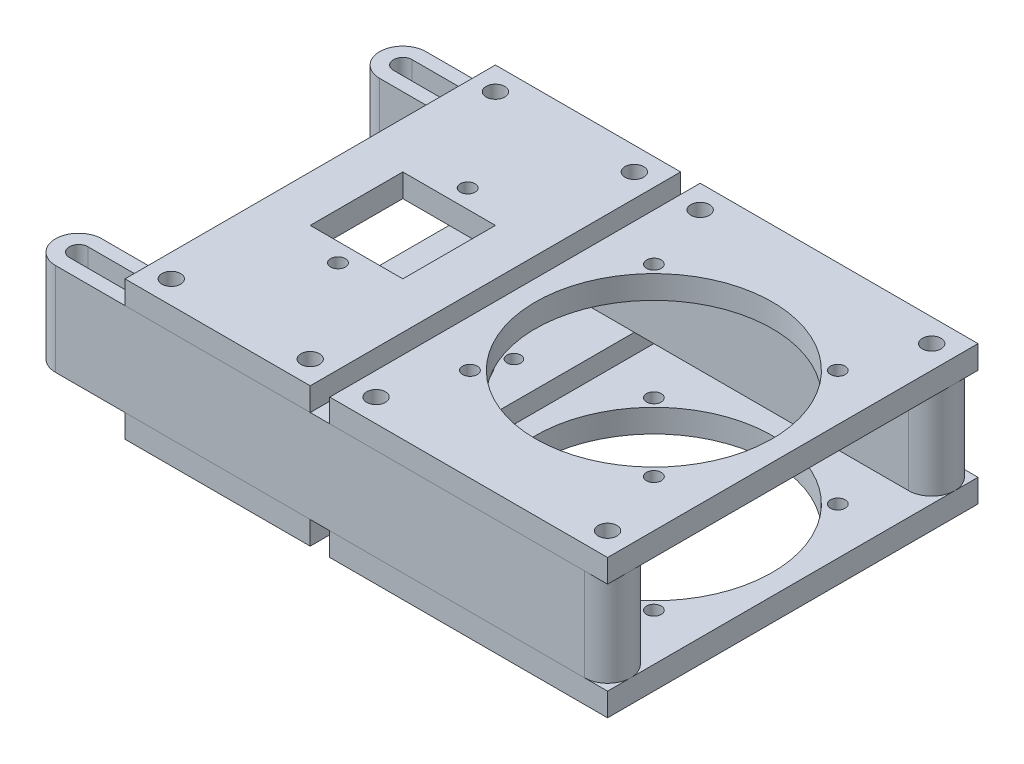
SolidWorks part; units mm, degrees
material "Alum Plate"
ref_plane "Front Plane" through (0, 0, 0) normal (0, 0, 1) x (1, 0, 0)
ref_plane "Top Plane" through (0, 0, 0) normal (0, 1, 0) x (1, 0, 0)
ref_plane "Right Plane" through (0, 0, 0) normal (1, 0, 0) x (0, 0, -1)
sketch "Sketch2" plane through (0, 0, 0) normal (0, 1, 0) x (1, 0, 0)
  line L0 (0, 0) -> (-68.8619, 0) construction
  line L1 (-38.1, -50.8) -> (-38.1, 50.8)
  line L2 (-38.1, 50.8) -> (38.1, 50.8)
  line L4 (-38.1, -50.8) -> (38.1, -50.8)
  line L5 (38.1, 50.8) -> (38.1, -50.8)
  line L7 (-94.2619, 50.8) -> (-43.4619, 50.8)
  line L8 (-81.5619, 12.7) -> (-56.1619, 12.7) construction
  line L9 (-81.5619, 12.7) -> (-81.5619, -12.7) construction
  line L10 (-81.5619, -12.7) -> (-56.1619, -12.7) construction
  line L11 (-56.1619, 12.7) -> (-56.1619, -12.7) construction
  line L12 (-81.5619, 12.7) -> (-56.1619, -12.7) construction
  line L13 (-81.5619, -12.7) -> (-56.1619, 12.7) construction
  line L14 (-38.1, -50.8) -> (38.1, 50.8) construction
  line L15 (-94.2619, 50.8) -> (-94.2619, -50.8)
  line L16 (-94.2619, -50.8) -> (-43.4619, -50.8)
  line L17 (-43.4619, 50.8) -> (-43.4619, -50.8)
  line L18 (-94.2619, 50.8) -> (-43.4619, -50.8) construction
  line L19 (-94.2619, -50.8) -> (-43.4619, 50.8) construction
  circle A0 centre (0, 0) radius 32.5
  circle A1 centre (-68.8619, 0) radius 18 construction
  point P5 (-34.431, 0)
  point P8 (-38.1, 0)
  dimension "D1" = 65
  dimension "D2" = 36
  dimension "D3" = 68.8619
  dimension "D4" = 38.1
  dimension "D5" = 50.8
  dimension "D6" = 25.4
  dimension "D7" = 25.4
  dimension "D8" = 50.8
extrude "Boss-Extrude1" add sketch "Sketch2" against normal blind 6.35 from offset 19.05
mirror "Mirror1" about plane through (0, 0, 0) normal (0, 1, 0) of bodies 101 109
sketch "Sketch3" plane through (0, 19.05, 0) normal (0, 1, 0) x (1, 0, 0)
  line L1 (-81.5619, -12.7) -> (-56.1619, -12.7)
  line L2 (-81.5619, -12.7) -> (-81.5619, 12.7)
  line L3 (-81.5619, 12.7) -> (-56.1619, 12.7)
  line L4 (-56.1619, -12.7) -> (-56.1619, 12.7)
  line L5 (-81.5619, -12.7) -> (-56.1619, 12.7) construction
  line L6 (-81.5619, 12.7) -> (-56.1619, -12.7) construction
  point P4 (-68.8619, 0)
extrude "Cut-Extrude1" cut sketch "Sketch3" against normal up to next (6.35 mm away)
sketch "Sketch4" plane through (0, -19.05, 0) normal (0, -1, 0) x (1, 0, 0)
  circle A0 centre (-68.8619, 0) radius 18 construction
  circle A1 centre (-68.8619, 0) radius 18
extrude "Cut-Extrude2" cut sketch "Sketch4" against normal up to next (6.35 mm away)
sketch "Sketch5" plane through (0, -19.05, 0) normal (0, -1, 0) x (1, 0, 0)
  line L1 (-84.1019, 15.24) -> (-53.6219, 15.24) construction
  line L2 (-84.1019, 15.24) -> (-84.1019, -15.24) construction
  line L3 (-84.1019, -15.24) -> (-53.6219, -15.24) construction
  line L4 (-53.6219, 15.24) -> (-53.6219, -15.24) construction
  line L5 (-84.1019, 15.24) -> (-53.6219, -15.24) construction
  line L6 (-84.1019, -15.24) -> (-53.6219, 15.24) construction
  circle A0 centre (-84.1019, 15.24) radius 1.905
  circle A1 centre (-53.6219, 15.24) radius 1.905
  circle A2 centre (-53.6219, -15.24) radius 1.905
  circle A3 centre (-84.1019, -15.24) radius 1.905
  point P0 (-68.8619, 0)
  dimension "D2" = 3.81
  dimension "D1" = 30.48
extrude "Cut-Extrude3" cut sketch "Sketch5" against normal up to next (6.35 mm away)
sketch "Sketch6" plane through (0, 19.05, 0) normal (0, 1, 0) x (1, 0, 0)
  line L0 (-38.1, -44.45) -> (-31.75, -44.45) construction
  line L2 (-31.75, -44.45) -> (-31.75, -50.8) construction
  line L3 (-38.1, -50.8) -> (38.1, -50.8) construction
  line L4 (-38.1, 44.45) -> (-31.75, 44.45) construction
  line L5 (-31.75, 44.45) -> (-31.75, 50.8) construction
  line L6 (38.1, 50.8) -> (-38.1, 50.8) construction
  line L7 (38.1, 44.45) -> (31.75, 44.45) construction
  line L8 (38.1, -50.8) -> (38.1, 50.8) construction
  line L9 (31.75, 44.45) -> (31.75, 50.8) construction
  line L10 (31.75, -50.8) -> (31.75, -44.45) construction
  line L11 (31.75, -44.45) -> (38.1, -44.45) construction
  line L12 (-38.1, 50.8) -> (-38.1, -50.8) construction
  line L13 (25.226, 25.226) -> (-25.226, 25.226) construction
  line L14 (25.226, 25.226) -> (25.226, -25.226) construction
  line L15 (25.226, -25.226) -> (-25.226, -25.226) construction
  line L16 (-25.226, 25.226) -> (-25.226, -25.226) construction
  line L17 (25.226, 25.226) -> (-25.226, -25.226) construction
  line L18 (25.226, -25.226) -> (-25.226, 25.226) construction
  line L19 (-49.8119, -50.8) -> (-49.8119, -44.45) construction
  line L20 (-94.2619, -50.8) -> (-43.4619, -50.8) construction
  line L21 (-49.8119, -44.45) -> (-43.4619, -44.45) construction
  line L22 (-43.4619, -50.8) -> (-43.4619, 50.8) construction
  line L23 (-68.8619, -50.8) -> (-68.8619, 50.8) construction
  line L24 (-43.4619, 50.8) -> (-94.2619, 50.8) construction
  line L25 (-94.2619, 0) -> (-43.4619, 0) construction
  line L26 (-94.2619, 50.8) -> (-94.2619, -50.8) construction
  circle A0 centre (-31.75, 44.45) radius 2.5527
  circle A1 centre (31.75, 44.45) radius 2.5527
  circle A2 centre (31.75, -44.45) radius 2.5527
  circle A3 centre (-31.75, -44.45) radius 2.5527
  circle A4 centre (-25.226, 25.226) radius 2.0193
  circle A5 centre (25.226, 25.226) radius 2.0193
  circle A6 centre (25.226, -25.226) radius 2.0193
  circle A7 centre (-25.226, -25.226) radius 2.0193
  circle A8 centre (0, 0) radius 32.5 construction
  circle A9 centre (-49.8119, -44.45) radius 2.5527
  circle A10 centre (-49.8119, 44.45) radius 2.5527
  circle A11 centre (-87.9119, -44.45) radius 2.5527
  circle A12 centre (-87.9119, 44.45) radius 2.5527
  point P24 (0, 0)
  point P34 (-22.981, 22.981)
  dimension "D2" = 5.1054
  dimension "D3" = 4.0386
  dimension "D1" = 6.35
  dimension "D4" = 3.175
extrude "Cut-Extrude4" cut sketch "Sketch6" against normal through all
sketch "Sketch7" plane through (0, 19.05, 0) normal (0, 1, 0) x (1, 0, 0)
  line L0 (-68.8619, 12.7) -> (-68.8619, 17.78) construction
  line L2 (-68.8619, -12.7) -> (-68.8619, -17.78) construction
  line L4 (-56.1619, 12.7) -> (-81.5619, 12.7) construction
  line L5 (-81.5619, -12.7) -> (-56.1619, -12.7) construction
  circle A0 centre (-68.8619, 17.78) radius 2.0193
  circle A1 centre (-68.8619, -17.78) radius 2.0193
  point P2 (-68.8619, 12.7)
  point P6 (-68.8619, -12.7)
  dimension "D1" = 4.0386
  dimension "D2" = 5.08
extrude "Cut-Extrude5" cut sketch "Sketch7" against normal up to next (6.35 mm away)
sketch "Sketch8" plane through (0, -12.7, 0) normal (0, 1, 0) x (1, 0, 0)
  line L0 (31.75, -44.45) -> (-113.3119, -44.45) construction
  line L1 (31.75, -50.8) -> (-113.3119, -50.8)
  line L2 (31.75, -38.1) -> (-113.3119, -38.1)
  line L3 (-94.2619, -50.8) -> (-43.4619, -50.8) construction
  line L4 (31.75, 44.45) -> (-113.3119, 44.45) construction
  line L5 (31.75, 38.1) -> (-113.3119, 38.1)
  line L6 (31.75, 50.8) -> (-113.3119, 50.8)
  line L7 (-43.4619, 50.8) -> (-94.2619, 50.8) construction
  line L8 (-113.3119, -44.45) -> (-113.3119, 44.45) construction
  line L9 (-49.8119, 44.45) -> (-113.3119, 44.45) construction
  line L10 (-49.8119, 41.8973) -> (-113.3119, 41.8973)
  line L11 (-49.8119, 47.0027) -> (-113.3119, 47.0027)
  line L12 (-49.8119, -44.45) -> (-113.3119, -44.45) construction
  line L13 (-49.8119, -47.0027) -> (-113.3119, -47.0027)
  line L14 (-49.8119, -41.8973) -> (-113.3119, -41.8973)
  arc A0 (31.75, -50.8) -> (31.75, -38.1) centre (31.75, -44.45) ccw
  arc A1 (-113.3119, -38.1) -> (-113.3119, -50.8) centre (-113.3119, -44.45) ccw
  arc A2 (31.75, 38.1) -> (31.75, 50.8) centre (31.75, 44.45) ccw
  arc A3 (-113.3119, 50.8) -> (-113.3119, 38.1) centre (-113.3119, 44.45) ccw
  arc A6 (-49.8119, 41.8973) -> (-49.8119, 47.0027) centre (-49.8119, 44.45) ccw
  arc A7 (-113.3119, 47.0027) -> (-113.3119, 41.8973) centre (-113.3119, 44.45) ccw
  arc A8 (-49.8119, -47.0027) -> (-49.8119, -41.8973) centre (-49.8119, -44.45) ccw
  arc A9 (-113.3119, -41.8973) -> (-113.3119, -47.0027) centre (-113.3119, -44.45) ccw
  circle A10 centre (-87.9119, 44.45) radius 2.5527 construction
  circle A11 centre (-87.9119, -44.45) radius 2.5527 construction
  point P3 (-40.781, -44.45)
  point P13 (-40.781, 44.45)
  point P23 (-87.9119, 44.45)
  point P24 (-81.5619, 44.45)
  point P32 (-81.5619, -44.45)
  dimension "D1" = 25.4
extrude "Boss-Extrude2" add sketch "Sketch8" along normal up to surface (25.4 mm away) separate body up to face at (-68.8619, 12.7, -15.7607)
